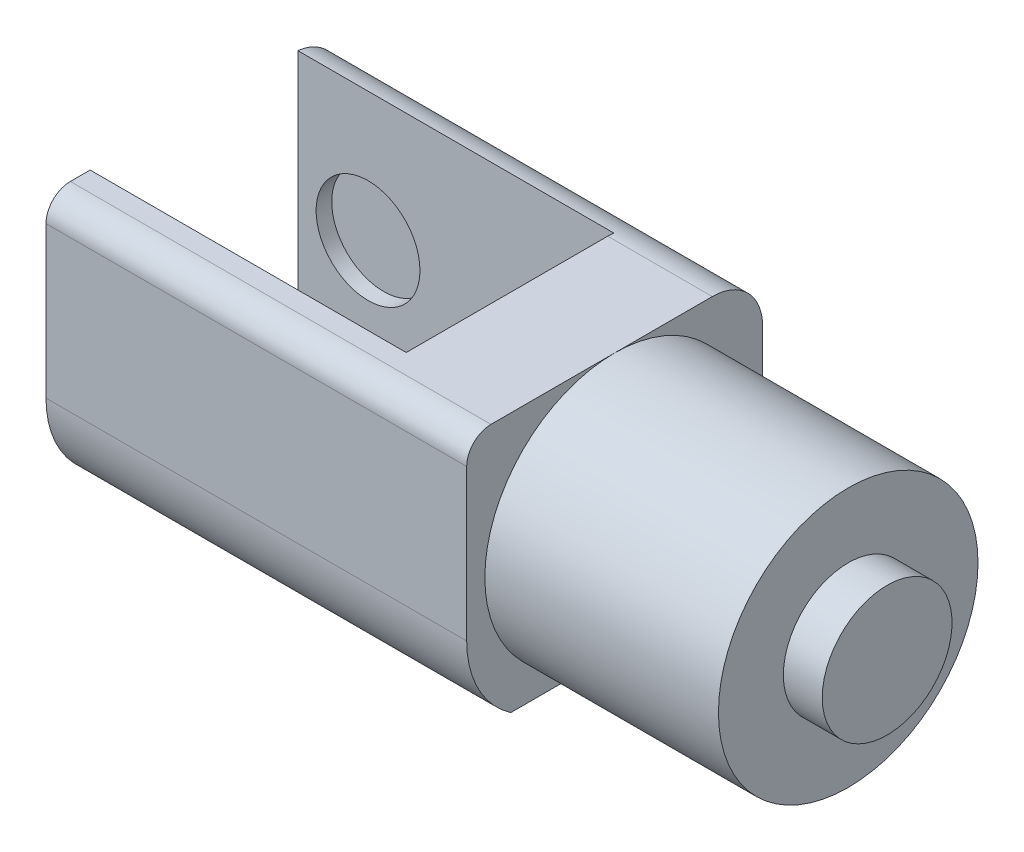
SolidWorks part; units mm, degrees
ref_plane "Front Plane" through (0, 0, 0) normal (0, 0, 1) x (1, 0, 0)
ref_plane "Top Plane" through (0, 0, 0) normal (0, 1, 0) x (1, 0, 0)
ref_plane "Right Plane" through (0, 0, 0) normal (1, 0, 0) x (0, 0, -1)
sketch "Sketch1" plane through (0, 0, 0) normal (1, 0, 0) x (0, 0, -1)
  circle A1 centre (0, 0) radius 12.7
  dimension "D1" = 25.4
extrude "Boss-Extrude1" add sketch "Sketch1" along normal blind 22.86
sketch "Sketch2" plane through (22.86, 0, 0) normal (1, 0, 0) x (0, 0, -1)
  circle A0 centre (0, 0) radius 6.35
  dimension "D1" = 12.7
extrude "Boss-Extrude2" add sketch "Sketch2" along normal blind 3.81
ref_plane "Plane2" through (0, 0, 10.16) normal (0, 0, 1) x (1, 0, 0)
sketch "Sketch4" plane through (0, 0, 10.16) normal (0, 0, 1) x (1, 0, 0)
  line L0 (0, 12.7) -> (0, -12.7) construction
  line L5 (0, 12.7) -> (-41.1679, 12.7)
  line L6 (0, 12.7) -> (0, -12.7)
  line L7 (0, -12.7) -> (-41.1679, -12.7)
  line L8 (-41.1679, 12.7) -> (-41.1679, -12.7)
extrude "Boss-Extrude4" add sketch "Sketch4" along normal blind 4.318
fillet "Fillet3" radius 2.38 1 edges at (-20.5839, 12.7, 14.478)
fillet "Fillet4" radius 10 1 edges at (-20.5839, -12.7, 14.478)
sketch "Sketch5" plane through (0, 0, 10.16) normal (0, 0, 1) x (1, 0, 0)
  line L1 (-41.1679, -12.7) -> (0, -12.7) construction
  line L2 (0, 12.7) -> (-10.2346, 12.7)
  line L3 (0, 12.7) -> (0, -12.7)
  line L4 (0, -12.7) -> (-10.2346, -12.7)
  line L5 (-10.2346, 12.7) -> (-10.2346, -12.7)
extrude "Boss-Extrude5" add sketch "Sketch5" against normal blind 20.32
ref_plane "Plane4" through (0, 0, -10.16) normal (0, 0, 1) x (1, 0, 0)
sketch "Sketch8" plane through (0, 0, -10.16) normal (0, 0, 1) x (1, 0, 0)
  line L1 (0, 12.7) -> (-41.1679, 12.7)
  line L2 (0, 12.7) -> (0, -12.7)
  line L3 (0, -12.7) -> (-41.1679, -12.7)
  line L4 (-41.1679, 12.7) -> (-41.1679, -12.7)
extrude "Boss-Extrude10" add sketch "Sketch8" against normal blind 4.318 contours L2 L1 L4 L3
fillet "Fillet12" radius 4.92 1 edges at (-20.5839, 12.7, -14.478)
fillet "Fillet13" radius 4.92 1 edges at (-20.5839, -12.7, -14.478)
sketch "Sketch9" plane through (0, 0, -10.16) normal (0, 0, 1) x (1, 0, 0)
  line L0 (0, 0) -> (-34.29, 0) construction
  circle A1 centre (-34.29, 0) radius 5.08
  dimension "D1" = 34.29
  dimension "D2" = 10.16
extrude "Cut-Extrude1" cut sketch "Sketch9" against normal blind 1.524
sketch "Sketch10" plane through (0, 0, 10.16) normal (0, 0, 1) x (1, 0, 0)
  line L0 (0, 0) -> (-34.29, 0) construction
  circle A0 centre (-34.29, 0) radius 5.08
extrude "Cut-Extrude3" cut sketch "Sketch10" along normal blind 1.524
